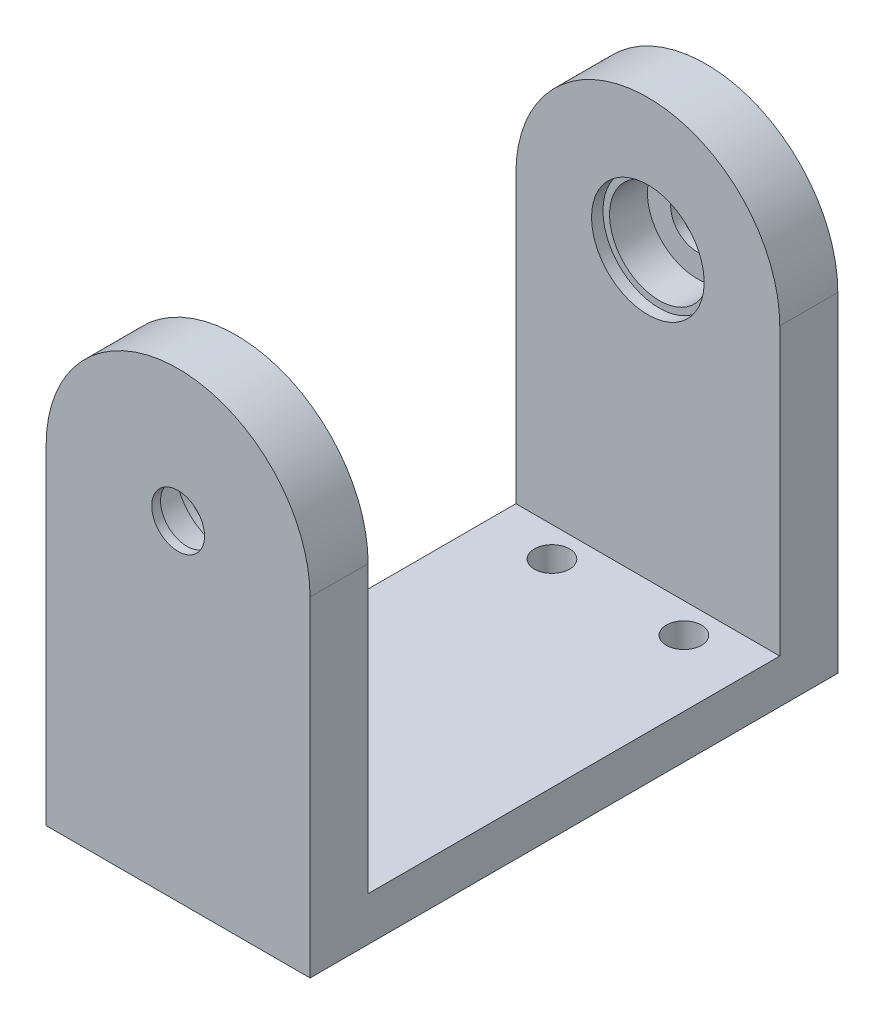
SolidWorks part; units mm, degrees
ref_plane "Front Plane" through (0, 0, 0) normal (0, 0, 1) x (1, 0, 0)
ref_plane "Top Plane" through (0, 0, 0) normal (0, 1, 0) x (1, 0, 0)
ref_plane "Right Plane" through (0, 0, 0) normal (1, 0, 0) x (0, 0, -1)
sketch "Sketch1" plane through (0, 0, 0) normal (0, 1, 0) x (1, 0, 0)
  line L0 (-1.3042, 0) -> (2.0884, 0) construction
  line L1 (0, 5.5134) -> (0, -5.3226) construction
  line L2 (15, 20) -> (-15, 20) construction
  line L3 (15, -30) -> (-15, -30)
  line L4 (15, -30) -> (15, 30)
  line L5 (15, 30) -> (-15, 30)
  line L6 (-15, -30) -> (-15, 30)
  line L7 (15, -30) -> (-15, 30) construction
  line L8 (15, 30) -> (-15, -30) construction
  line L9 (15, -20) -> (-15, -20) construction
  circle A0 centre (-7.5, 20) radius 2
  circle A1 centre (7.5, 20) radius 2
  circle A2 centre (7.5, -20) radius 2
  circle A3 centre (-7.5, -20) radius 2
  point P4 (0, 0)
  dimension "D4" = 4
  dimension "D1" = 10
  dimension "D2" = 40
  dimension "D3" = 30
  dimension "D5" = 15
extrude "Boss-Extrude1" add sketch "Sketch1" along normal blind 5
ref_plane "Plane1" through (0, 0, 30) normal (0, 0, 1) x (1, 0, 0)
sketch "Sketch3" plane through (0, 0, 30) normal (0, 0, 1) x (1, 0, 0)
  line L0 (-15, 5) -> (15, 5)
  line L1 (15, 5) -> (15, 0) construction
  line L2 (-15, 5) -> (15, 5) construction
  line L3 (15, 5) -> (15, 37.5)
  line L4 (-15, 5) -> (-15, 37.5)
  arc A0 (-15, 37.5) -> (15, 37.5) centre (0, 37.5) cw
  circle A1 centre (0, 37.5) radius 3
  circle A2 centre (0, 37.5) radius 22.5 construction
  dimension "D1" = 6
  dimension "D3" = 45
  dimension "D2" = 37.5
extrude "Boss-Extrude2" add sketch "Sketch3" against normal blind 6.6
sketch "Sketch4" plane through (0, 0, 23.4) normal (0, 0, -1) x (-1, 0, 0)
  circle A0 centre (0, 37.5) radius 6.4
  dimension "D1" = 12.8
extrude "Cut-Extrude1" cut sketch "Sketch4" against normal blind 1.3
sketch "Sketch6" plane through (0, 0, 24.7) normal (0, 0, -1) x (-1, 0, 0)
  circle A0 centre (0, 37.5) radius 5.65
  dimension "D1" = 11.3
extrude "Cut-Extrude2" cut sketch "Sketch6" against normal blind 4.3
mirror "Mirror2" about plane through (0, 0, 0) normal (0, 0, 1) of "Cut-Extrude2", "Cut-Extrude1", "Boss-Extrude2"
